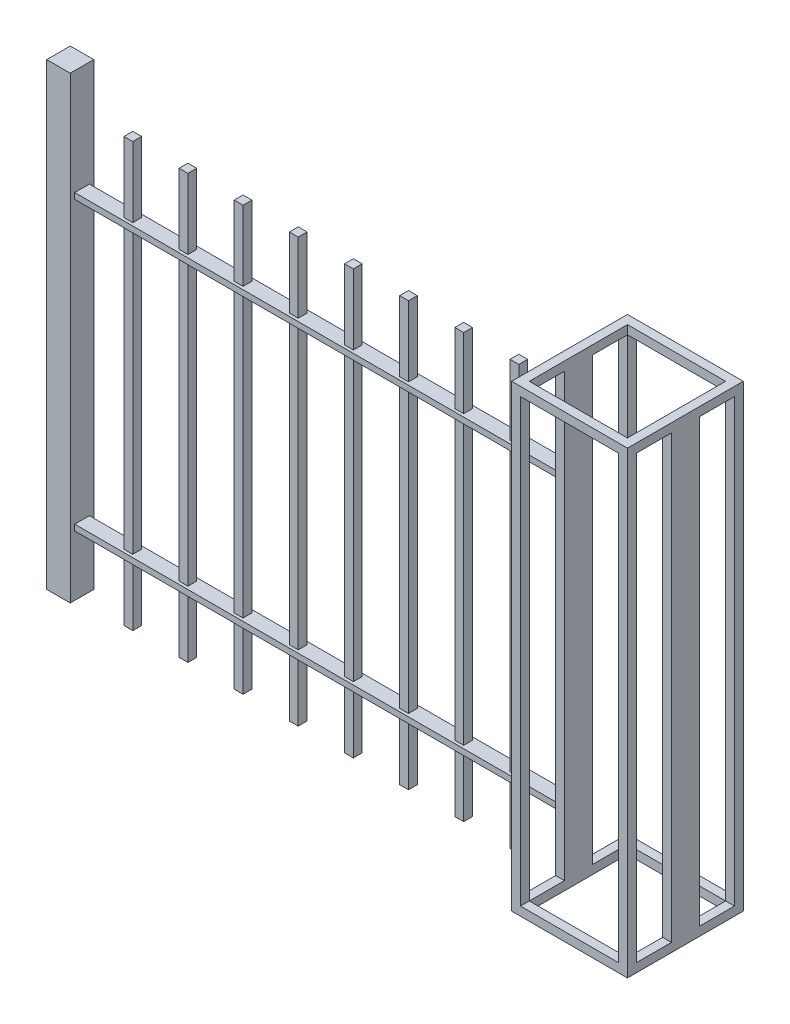
SolidWorks part; units mm, degrees
ref_plane "Front Plane" through (0, 0, 0) normal (0, 0, 1) x (1, 0, 0)
ref_plane "Top Plane" through (0, 0, 0) normal (0, 1, 0) x (1, 0, 0)
ref_plane "Right Plane" through (0, 0, 0) normal (1, 0, 0) x (0, 0, -1)
sketch "Sketch1" plane through (0, 0, 0) normal (0, 1, 0) x (1, 0, 0)
  line L0 (-3298, 30) -> (-3278.95, 30)
  line L1 (-4401.2, 25.4) -> (-4350.4, 25.4)
  line L2 (-3048, 0) -> (3048, 0) construction
  line L3 (-4401.2, 25.4) -> (-4401.2, -25.4)
  line L4 (-3048, 0) -> (-7519.7981, 0) construction
  line L5 (-4401.2, -25.4) -> (-4350.4, -25.4)
  line L6 (3048, 0) -> (9276.729, 0) construction
  line L7 (-3298, -105.95) -> (-3278.95, -105.95)
  line L8 (-3298, -125) -> (-3048, -125)
  line L9 (-3298, -125) -> (-3298, 125)
  line L10 (-3298, 125) -> (-3048, 125)
  line L11 (-3048, -125) -> (-3048, 125)
  line L12 (-3298, -125) -> (-3048, 125) construction
  line L13 (-3298, 125) -> (-3048, -125) construction
  line L14 (-3278.95, -105.95) -> (-3278.95, -125)
  line L15 (-3067.05, -125) -> (-3067.05, -105.95)
  line L16 (-3067.05, -105.95) -> (-3048, -105.95)
  line L17 (-3298, 105.95) -> (-3278.95, 105.95)
  line L18 (-3278.95, 105.95) -> (-3278.95, 125)
  line L19 (-3048, 105.95) -> (-3067.05, 105.95)
  line L20 (-3067.05, 105.95) -> (-3067.05, 125)
  line L21 (-3536.1, 9.525) -> (-3536.1, -9.525)
  line L22 (-3278.95, 105.95) -> (-3067.05, 105.95)
  line L23 (-3278.95, 105.95) -> (-3278.95, -105.95)
  line L24 (-3278.95, -105.95) -> (-3067.05, -105.95)
  line L25 (-3067.05, 105.95) -> (-3067.05, -105.95)
  line L26 (-3417.05, 9.525) -> (-3398, 9.525)
  line L27 (-3417.05, 9.525) -> (-3417.05, -9.525)
  line L28 (-3417.05, -9.525) -> (-3398, -9.525)
  line L29 (-3398, 9.525) -> (-3398, -9.525)
  line L30 (-3417.05, 9.525) -> (-3398, -9.525) construction
  line L31 (-3417.05, -9.525) -> (-3398, 9.525) construction
  line L32 (-3536.1, 9.525) -> (-3517.05, 9.525)
  line L33 (-3517.05, 9.525) -> (-3517.05, -9.525)
  line L34 (-3536.1, -9.525) -> (-3517.05, -9.525)
  line L35 (-3655.15, 9.525) -> (-3655.15, -9.525)
  line L36 (-3655.15, 9.525) -> (-3636.1, 9.525)
  line L37 (-3636.1, 9.525) -> (-3636.1, -9.525)
  line L38 (-3655.15, -9.525) -> (-3636.1, -9.525)
  line L39 (-3774.2, 9.525) -> (-3774.2, -9.525)
  line L40 (-3774.2, 9.525) -> (-3755.15, 9.525)
  line L41 (-3755.15, 9.525) -> (-3755.15, -9.525)
  line L42 (-3774.2, -9.525) -> (-3755.15, -9.525)
  line L43 (-3893.25, 9.525) -> (-3893.25, -9.525)
  line L44 (-3893.25, 9.525) -> (-3874.2, 9.525)
  line L45 (-3874.2, 9.525) -> (-3874.2, -9.525)
  line L46 (-3893.25, -9.525) -> (-3874.2, -9.525)
  line L47 (-4012.3, 9.525) -> (-4012.3, -9.525)
  line L48 (-4012.3, 9.525) -> (-3993.25, 9.525)
  line L49 (-3993.25, 9.525) -> (-3993.25, -9.525)
  line L50 (-4012.3, -9.525) -> (-3993.25, -9.525)
  line L51 (-4131.35, 9.525) -> (-4131.35, -9.525)
  line L52 (-4131.35, 9.525) -> (-4112.3, 9.525)
  line L53 (-4112.3, 9.525) -> (-4112.3, -9.525)
  line L54 (-4131.35, -9.525) -> (-4112.3, -9.525)
  line L55 (-4250.4, 9.525) -> (-4250.4, -9.525)
  line L56 (-4250.4, 9.525) -> (-4231.35, 9.525)
  line L57 (-4231.35, 9.525) -> (-4231.35, -9.525)
  line L58 (-4250.4, -9.525) -> (-4231.35, -9.525)
  line L59 (-4350.4, 25.4) -> (-4350.4, -25.4)
  line L60 (-4401.2, 25.4) -> (-4350.4, -25.4) construction
  line L61 (-4401.2, -25.4) -> (-4350.4, 25.4) construction
  line L62 (-3067.05, 30) -> (-3048, 30)
  line L63 (-3067.05, -30) -> (-3048, -30)
  line L64 (-3298, -30) -> (-3278.95, -30)
  line L65 (-2997.2, 0) -> (-2159, 0)
  line L66 (-2997.2, 0) -> (-2997.2, -838.2)
  line L67 (-2159, 0) -> (-3552, -353.6) construction
  line L68 (-3552, -353.6) -> (-2997.2, -838.2) construction
  line L69 (-2997.2, 0) -> (-2482.5868, -661.6286)
  line L70 (-3552, -353.6) -> (-2482.5868, -661.6286) construction
  line L71 (-2997.2, 0) -> (0, 0)
  line L72 (-2997.2, 0) -> (-2997.2, -2997.2)
  line L73 (-2997.2, 0) -> (-1157.0679, -2365.8237)
  point P0 (-4375.8, 0)
  point P2 (-3173, 0)
  point P25 (-3407.525, 0)
  point P34 (-2392.5012, -651.6597)
  point P69 (-10.9068, -255.4619)
  point P78 (-2498.1811, -641.5793)
  dimension "D1" = 6096
  dimension "D4" = 19.05
  dimension "D3" = 250
  dimension "D2" = 100
  dimension "D6" = 100
  dimension "D7" = 50.8
  dimension "D8" = 100
  dimension "D9" = 60
  dimension "D10" = 50.8
  dimension "D11" = 228.6
  dimension "D12" = 254
  dimension "D14" = 736.6412
  dimension "D13" = 838.2
  dimension "D15" = 1437.1785
  dimension "D16" = 48.864
  dimension "D17" = 97.5699
  dimension "D18" = 1112.891
  dimension "D5" = 8
extrude "Boss-Extrude1" add sketch "Sketch1" along normal blind 990.6 contours L20 L19 L11 L10 | L16 L15 L8 L11 | L17 L18 L10 L9 | L14 L7 L9 L8 | L59 L1 L3 L5 | L25 L63 L11 L62 | L9 L64 L23 L0 region at (-3288.475, 0, 0) region at (-3288.475, 0, -115.475) region at (-3288.475, 0, 115.475) region at (-3057.525, 0, -115.475) region at (-3057.525, 0, 0) region at (-3057.525, 0, 115.475) region at (-4375.8, 0, 0)
extrude "Boss-Extrude2" add sketch "Sketch1<3>" against normal blind 19.05 from surface contours L24 L14 L8 L15 | L19 L25 L16 L11 | L18 L22 L20 L10 | L23 L17 L9 L7 | L25 L62 L11 L19 | L63 L25 L16 L11 | L23 L17 L9 L0 | L64 L9 L7 L23 region at (-3288.475, 0, -67.975) region at (-3288.475, 0, 67.975) region at (-3173, 0, -115.475) region at (-3057.525, 0, -67.975) region at (-3173, 0, 115.475) region at (-3057.525, 0, 67.975) starting at face at (-3057.525, 990.6, 115.475)
sketch "Sketch1<3>" plane through (0, 0, 0) normal (0, 1, 0) x (1, 0, 0) same geometry as "Sketch1"
extrude "Boss-Extrude3" add sketch "Sketch1<4>" along normal blind 19.05 contours L19 L25 L16 L11 | L18 L22 L20 L10 | L23 L17 L9 L7 | L24 L14 L8 L15 | L25 L62 L11 L19 | L63 L25 L16 L11 | L23 L17 L9 L0 | L64 L9 L7 L23 region at (-3288.475, 0, -67.975) region at (-3288.475, 0, 67.975) region at (-3173, 0, -115.475) region at (-3057.525, 0, -67.975) region at (-3173, 0, 115.475) region at (-3057.525, 0, 67.975)
sketch "Sketch1<4>" plane through (0, 0, 0) normal (0, 1, 0) x (1, 0, 0) same geometry as "Sketch1"
extrude "Boss-Extrude4" add sketch "Sketch1<5>" along normal blind 914.4 separate body contours L29 L28 L27 L26 | L33 L34 L21 L32 | L37 L38 L35 L36 | L41 L42 L39 L40 | L45 L46 L43 L44 | L50 L49 L48 L47 | L54 L53 L52 L51 | L58 L57 L56 L55
sketch "Sketch1<5>" plane through (0, 0, 0) normal (0, 1, 0) x (1, 0, 0) same geometry as "Sketch1"
sketch "Sketch2" plane through (0, 0, 0) normal (0, 1, 0) x (1, 0, 0)
  line L1 (-4350.4, 15.875) -> (-3298, 15.875)
  line L2 (-4350.4, 15.875) -> (-4350.4, -15.875)
  line L3 (-4350.4, -15.875) -> (-3298, -15.875)
  line L4 (-3298, 15.875) -> (-3298, -15.875)
  line L5 (-3298, -125) -> (-3298, 125) construction
  line L8 (-4350.4, 25.4) -> (-4350.4, 15.875) construction
  line L9 (-4350.4, -25.4) -> (-4350.4, -15.875) construction
  dimension "D1" = 31.75
extrude "Boss-Extrude5" add sketch "Sketch2" along normal blind 12.7 from offset 130
extrude "Boss-Extrude6" add sketch "Sketch2<2>" along normal blind 12.7 from offset 750
sketch "Sketch2<2>" plane through (0, 0, 0) normal (0, 1, 0) x (1, 0, 0) same geometry as "Sketch2"
equation "\"thin_bar\"= 0.75in"
equation "\"D4@Sketch1\"=\"thin_bar\""
equation "\"thick_bar\"= 2in"
equation "\"D7@Sketch1\"=\"thick_bar\""
